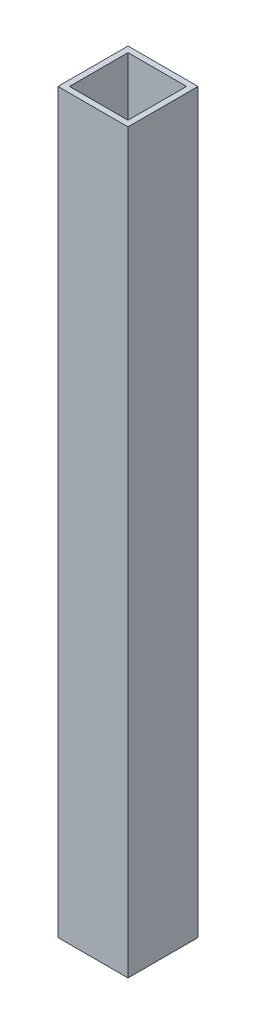
SolidWorks part; units mm, degrees
ref_plane "Front Plane" through (0, 0, 0) normal (0, 0, 1) x (1, 0, 0)
ref_plane "Top Plane" through (0, 0, 0) normal (0, 1, 0) x (1, 0, 0)
ref_plane "Right Plane" through (0, 0, 0) normal (1, 0, 0) x (0, 0, -1)
sketch "Sketch1" plane through (0, 0, 0) normal (0, 1, 0) x (1, 0, 0)
  line L0 (-8.0645, 8.0645) -> (8.0645, 8.0645)
  line L1 (-9.652, 9.652) -> (9.652, 9.652)
  line L2 (-9.652, 9.652) -> (-9.652, -9.652)
  line L3 (-9.652, -9.652) -> (9.652, -9.652)
  line L4 (9.652, 9.652) -> (9.652, -9.652)
  line L5 (-9.652, 9.652) -> (9.652, -9.652) construction
  line L6 (-9.652, -9.652) -> (9.652, 9.652) construction
  line L7 (8.0645, 8.0645) -> (8.0645, -8.0645)
  line L8 (-8.0645, -8.0645) -> (8.0645, -8.0645)
  line L9 (-8.0645, 8.0645) -> (-8.0645, -8.0645)
  point P0 (0, 0)
  dimension "D1" = 19.304
  dimension "D2" = 1.5875
extrude "Boss-Extrude1" add sketch "Sketch1" along normal mid plane 203.2
